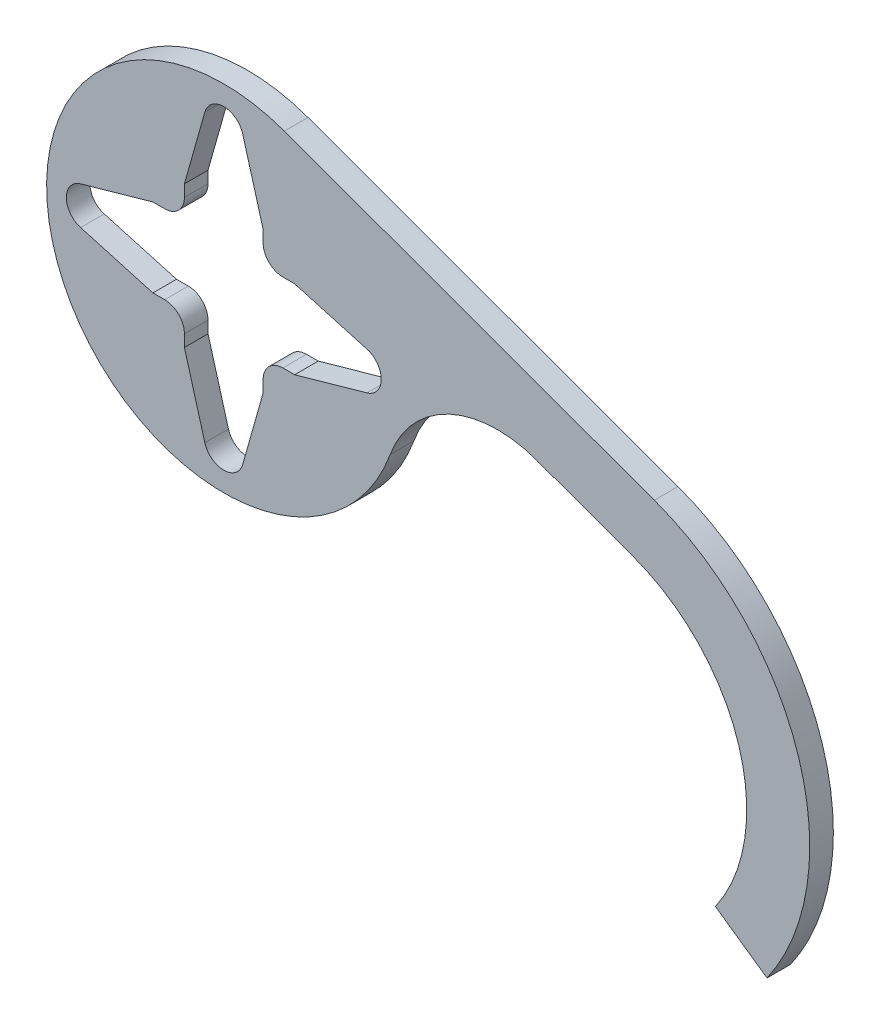
SolidWorks part; units mm, degrees
ref_plane "Front Plane" through (0, 0, 0) normal (0, 0, 1) x (1, 0, 0)
ref_plane "Top Plane" through (0, 0, 0) normal (0, 1, 0) x (1, 0, 0)
ref_plane "Right Plane" through (0, 0, 0) normal (1, 0, 0) x (0, 0, -1)
sketch "Sketch1" plane through (0, 0, 0) normal (0, 0, 1) x (1, 0, 0)
  line L0 (-5, 5) -> (-5, 9)
  line L8 (5, -5) -> (-5, -5)
  line L9 (5, -5) -> (5, 5)
  line L10 (5, 5) -> (-5, 5)
  line L11 (-5, -5) -> (-5, 5)
  line L12 (5, -5) -> (-5, 5) construction
  line L13 (5, 5) -> (-5, -5) construction
  line L14 (-5, 9) -> (-2.4058, 18.1799)
  line L15 (0, -55) -> (0, 55) construction
  line L16 (9, 5) -> (18.1799, 2.4058)
  line L17 (5, 5) -> (5, 9)
  line L18 (55, 0) -> (-55, 0) construction
  line L19 (5, -5) -> (5, -9)
  line L20 (-5, -9) -> (-2.4058, -18.1799)
  line L21 (5, -9) -> (2.4058, -18.1799)
  line L22 (-5, -5) -> (-5, -9)
  line L23 (5, -5) -> (9, -5)
  line L24 (9, -5) -> (18.1799, -2.4058)
  line L25 (-9, -5) -> (-18.1799, -2.4058)
  line L26 (5, 5) -> (9, 5)
  line L27 (-5, -5) -> (-9, -5)
  line L28 (-9, 5) -> (-18.1799, 2.4058)
  line L29 (5, 9) -> (2.4058, 18.1799)
  line L30 (-5, 5) -> (-9, 5)
  line L31 (0, 22.5) -> (-22.5, 0)
  line L32 (-22.5, 0) -> (-22.5, 22.5)
  line L33 (-22.5, 22.5) -> (0, 22.5)
  line L34 (-27.0416, 0) -> (-22.5, 0)
  line L35 (-22.5, 22.5) -> (-162.5, 22.5)
  line L36 (-22.5, 22.5) -> (-22.5, 0)
  line L37 (-22.5, 0) -> (-117.5, 0)
  line L38 (-162.5, 22.5) -> (-162.5, -11.5)
  line L41 (-22.5, 0) -> (-22.125, -4.0909)
  line L44 (-137.5, -11.5) -> (-137.5, -26.5)
  line L45 (-137.5, -26.5) -> (-117.5, -26.5)
  line L46 (-117.5, 0) -> (-117.5, -26.5)
  line L48 (-137.5, -11.5) -> (-162.5, -11.5)
  circle A0 centre (0, 0) radius 22.5
  circle A1 centre (0, 17.5) radius 2.5
  circle A2 centre (0, -17.5) radius 2.5
  circle A3 centre (17.5, 0) radius 2.5
  circle A4 centre (-17.5, 0) radius 2.5
  circle A5 centre (-7.5, 7.5) radius 2.5
  circle A6 centre (-7.5, -7.5) radius 2.5
  circle A7 centre (7.5, 7.5) radius 2.5
  circle A8 centre (7.5, -7.5) radius 2.5
  arc A9 (-27.0416, 0) -> (-22.125, -4.0909) centre (-27.0416, -5) cw
  dimension "D1" = 45
  dimension "D3" = 5
  dimension "D5" = 12.5
  dimension "D6" = 5
  dimension "D9" = 5
  dimension "D11" = 5
  dimension "D2" = 10
  dimension "D4" = 4
  dimension "D7" = 4
  dimension "D8" = 12.5
  dimension "D10" = 140
  dimension "D12" = 15
  dimension "D13" = 20
  dimension "D14" = 25
  dimension "D15" = 34
extrude "Boss-Extrude1" add sketch "Sketch1" along normal blind 3 contours A0 A4 L30 L0 A1 L17 L26 A3 L23 L19 A2 L22 L27 | A5 | A7 | A8 | A6 | L33 L31 L32 | L36 L37 L46 L45 L44 L48 L38 L35 | L41 A9 L34 region at (15.4599, 15.4599, 0)
sketch "Sketch3" [suppressed] plane through (0, 0, 3) normal (0, 0, 1) x (1, 0, 0)
  circle A0 centre (0, 0) radius 5
  circle A1 centre (0, 0) radius 22.5
  arc A2 (-22.125, -4.0909) -> (0, 22.5) centre (0, 0) ccw construction
  dimension "D1" = 10
extrude "Boss-Extrude2" [suppressed] add sketch "Sketch3" against normal up to surface (3 mm away) up to face at (-95.0076, -6.4219, 0)
sketch "Sketch4" plane through (0, 0, 3) normal (0, 0, 1) x (1, 0, 0)
  line L0 (-162.5, 22.5) -> (0, 22.5) construction
  line L3 (-162.5, 22.5) -> (0, 22.5)
  line L7 (-27.0416, 0) -> (-117.5, 0) construction
  line L8 (-117.5, 0) -> (-117.5, -26.5) construction
  line L9 (-137.5, -26.5) -> (-117.5, -26.5) construction
  line L10 (-137.5, -11.5) -> (-137.5, -26.5) construction
  line L11 (-137.5, -11.5) -> (-162.5, -11.5) construction
  line L12 (-162.5, 22.5) -> (-162.5, -11.5) construction
  line L13 (-27.0416, 0) -> (-117.5, 0)
  line L14 (-117.5, 0) -> (-117.5, -26.5)
  line L15 (-137.5, -26.5) -> (-117.5, -26.5)
  line L16 (-137.5, -11.5) -> (-137.5, -26.5)
  line L17 (-137.5, -11.5) -> (-162.5, -11.5)
  line L18 (-162.5, 22.5) -> (-162.5, -11.5)
  arc A0 (0, 22.5) -> (-22.125, -4.0909) centre (0, 0) ccw
  arc A1 (-22.125, -4.0909) -> (0, 22.5) centre (0, 0) ccw construction
  arc A2 (-22.125, -4.0909) -> (-27.0416, 0) centre (-27.0416, -5) ccw construction
  arc A3 (-22.125, -4.0909) -> (-27.0416, 0) centre (-27.0416, -5) ccw
extrude "Cut-Extrude1" cut sketch "Sketch4" against normal through all
sketch "Sketch5" [suppressed] plane through (0, 0, 0) normal (0, 0, -1) x (-1, 0, 0)
  circle A0 centre (0, 0) radius 5
  circle A2 centre (0, 0) radius 22.5
  circle A5 centre (0, 0) radius 22.5 construction
  dimension "D1" = 10
extrude "Boss-Extrude3" [suppressed] add sketch "Sketch5" against normal up to surface (3 mm away) up to face at (22.5, 0, 3)
sketch "Sketch6" plane through (0, 0, 3) normal (0, 0, 1) x (1, 0, 0)
  line L0 (7.6955, 21.1431) -> (54.6801, 4.0421)
  line L1 (68.994, -41.356) -> (62.4408, -36.7674)
  line L2 (39.7279, 0.9708) -> (51.9439, -3.4755)
  line L3 (7.6955, 21.1431) -> (0, 0) construction
  line L4 (0, 0) -> (21.1431, -7.6955) construction
  line L5 (0, -1000) -> (0, 49000) construction
  arc A0 (54.6801, 4.0421) -> (68.994, -41.356) centre (44.4195, -24.1487) cw
  arc A2 (21.1431, -7.6955) -> (7.6955, 21.1431) centre (0, 0) ccw
  arc A3 (51.9439, -3.4755) -> (62.4408, -36.7674) centre (44.4195, -24.1487) cw
  circle A4 centre (0, 0) radius 22.5 construction
  arc A5 (21.1431, -7.6955) -> (39.7279, 0.9708) centre (34.7686, -12.6547) cw
  dimension "D2" = 22
  dimension "D1" = 8
  dimension "D3" = 50
  dimension "D4" = 20
  dimension "D5" = 15
extrude "Boss-Extrude4" add sketch "Sketch6" against normal up to surface (3 mm away) up to face at (22.5, 0, 0)
sketch "Sketch7" [suppressed] plane through (0, 0, 3) normal (0, 0, 1) x (1, 0, 0)
  line L0 (54.6801, 4.0421) -> (51.9439, -3.4755)
  line L1 (54.6801, 4.0421) -> (7.6955, 21.1431) construction
  line L2 (39.7279, 0.9708) -> (51.9439, -3.4755) construction
  line L3 (39.7279, 0.9708) -> (51.9439, -3.4755)
  line L4 (54.6801, 4.0421) -> (7.6955, 21.1431)
  arc A0 (39.7279, 0.9708) -> (21.1431, -7.6955) centre (34.7686, -12.6547) ccw construction
  arc A1 (7.6955, 21.1431) -> (21.1431, -7.6955) centre (0, 0) ccw construction
  arc A2 (39.7279, 0.9708) -> (21.1431, -7.6955) centre (34.7686, -12.6547) ccw
  arc A3 (7.6955, 21.1431) -> (21.1431, -7.6955) centre (0, 0) ccw
extrude "Cut-Extrude2" [suppressed] cut sketch "Sketch7" against normal through all
ref_plane "Plane1" through (0, 0, 1.5) normal (0, 0, -1) x (-1, 0, 0)
